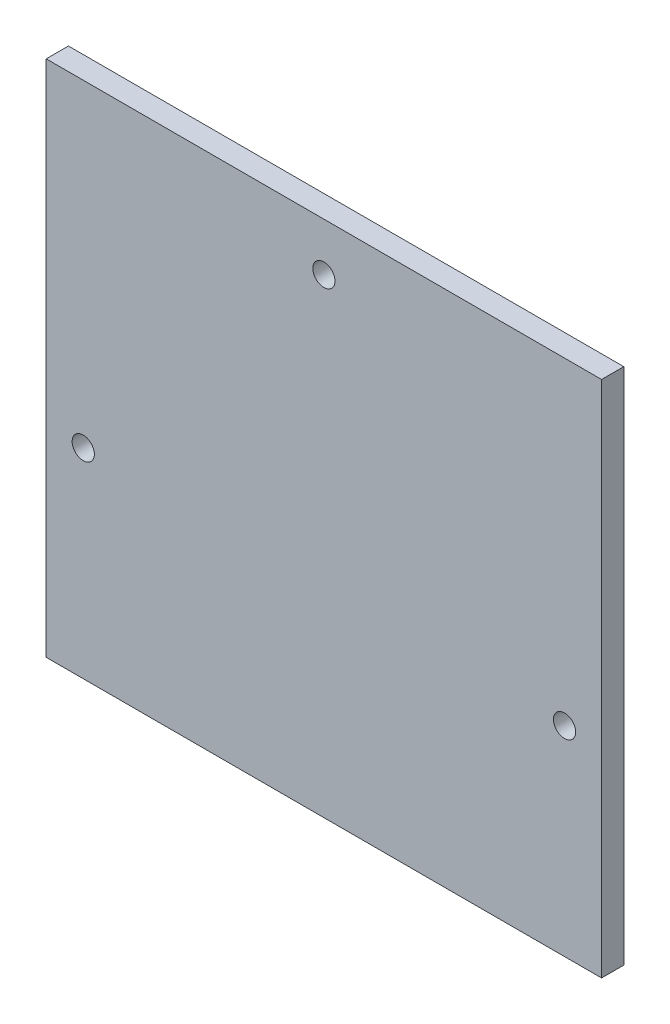
SolidWorks part; units mm, degrees
ref_plane "Plan de face" through (0, 0, 0) normal (0, 0, 1) x (1, 0, 0)
ref_plane "Plan de dessus" through (0, 0, 0) normal (0, 1, 0) x (1, 0, 0)
ref_plane "Plan de droite" through (0, 0, 0) normal (1, 0, 0) x (0, 0, -1)
sketch "Esquisse1" plane through (0, 0, 0) normal (0, 0, 1) x (1, 0, 0)
  line L0 (37.5, 87.7045) -> (37.5, -11.8594) construction
  line L1 (0, 0) -> (75, 0)
  line L2 (0, 0) -> (0, 70)
  line L3 (0, 70) -> (75, 70)
  line L4 (75, 0) -> (75, 70)
  circle A0 centre (5, 27) radius 1.5
  circle A1 centre (70, 27) radius 1.5
  circle A2 centre (37.5, 63.5) radius 1.5
  dimension "D3" = 3
  dimension "D1" = 70
  dimension "D2" = 75
  dimension "D4" = 5
  dimension "D5" = 27
  dimension "D6" = 37.5
  dimension "D7" = 6.5
extrude "Boss.-Extru.1" add sketch "Esquisse1" along normal blind 3
